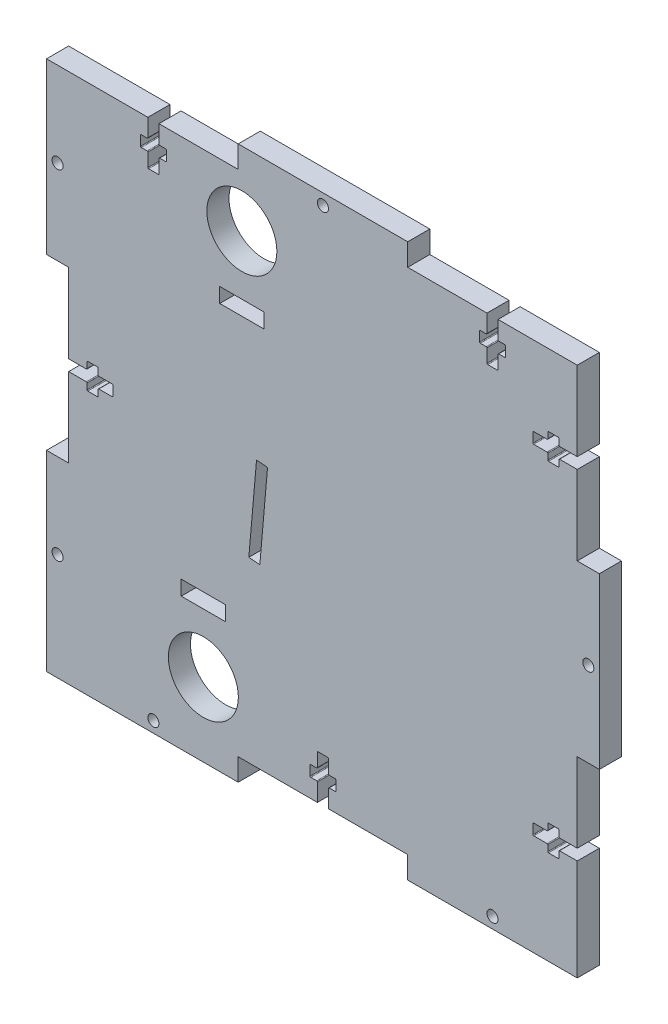
SolidWorks part; units mm, degrees
ref_plane "Front Plane" through (0, 0, 0) normal (0, 0, 1) x (1, 0, 0)
ref_plane "Top Plane" through (0, 0, 0) normal (0, 1, 0) x (1, 0, 0)
ref_plane "Right Plane" through (0, 0, 0) normal (1, 0, 0) x (0, 0, -1)
sketch "Sketch1" plane through (0, 0, 0) normal (0, 0, 1) x (1, 0, 0)
  line L0 (-69, 69) -> (-23, 69)
  line L5 (-75, -75) -> (75, -75) construction
  line L6 (-75, -75) -> (-75, 75) construction
  line L7 (-75, 75) -> (75, 75) construction
  line L8 (75, -75) -> (75, 75) construction
  line L9 (75, 23) -> (69, 23)
  line L10 (69, -23) -> (75, -23)
  line L11 (-69, -69) -> (69, -69) construction
  line L12 (-69, -69) -> (-69, 69) construction
  line L13 (-69, 69) -> (69, 69) construction
  line L14 (69, -69) -> (69, 69) construction
  line L15 (-69, -69) -> (69, 69) construction
  line L16 (69, -69) -> (69, -23)
  line L17 (-23, 69) -> (-23, 75)
  line L18 (-23, 75) -> (23, 75)
  line L19 (23, 75) -> (23, 69)
  line L20 (23, 69) -> (69, 69)
  line L21 (75, -23) -> (75, 23)
  line L22 (69, 23) -> (69, 69)
  line L23 (-75, 23) -> (-69, 23)
  line L24 (-69, 69) -> (-75, 69)
  line L25 (-75, 69) -> (-75, 23)
  line L26 (69, -69) -> (69, -75)
  line L27 (69, -75) -> (23, -75)
  line L28 (23, -75) -> (23, -69)
  line L29 (23, -69) -> (-23, -69)
  line L30 (-23, -69) -> (-23, -75)
  line L31 (-23, -75) -> (-69, -75)
  line L32 (-69, -75) -> (-69, -69) construction
  line L33 (-69, 23) -> (-69, -23)
  line L34 (-69, -23) -> (-75, -23)
  line L35 (-75, -23) -> (-75, -69)
  line L36 (-75, -69) -> (-69, -69) construction
  line L37 (-46, 69) -> (-46, -75) construction
  line L38 (-69, 69) -> (69, -69) construction
  line L39 (-75, -75) -> (-69, -75)
  line L40 (-75, -75) -> (-75, -69)
  point P0 (0, 0)
  point P6 (-7, -7)
  point P26 (0, -75)
  point P27 (-75, 0)
  dimension "D1" = 150
  dimension "D2" = 150
  dimension "D5" = 46
  dimension "D3" = 6
  dimension "D6" = 6
  dimension "D7" = 6
extrude "Box Side" add sketch "Sketch1" along normal blind 6
sketch "Sketch2" plane through (0, 0, 6) normal (0, 0, 1) x (1, 0, 0)
  line L0 (23, 72) -> (-23, 72) construction
  line L1 (23, 75) -> (23, 69) construction
  line L2 (-23, 69) -> (-23, 75) construction
  line L3 (-46, 69) -> (-46, -75) construction
  line L5 (0, 75) -> (0, 69) construction
  line L6 (-23, 75) -> (23, 75) construction
  line L7 (-69, 69) -> (69, 69) construction
  line L16 (-46, 69) -> (-46, -75) construction
  line L21 (0, -69) -> (0, 69) construction
  line L35 (-69, 69) -> (-23, 69) construction
  line L36 (-44.5, 69) -> (-44.5, 64.2)
  line L37 (-44.3, 64) -> (-42.7, 64)
  line L38 (-42.5, 63.8) -> (-42.5, 61.2)
  line L39 (-42.7, 61) -> (-44.3, 61)
  line L40 (-44.5, 60.8) -> (-44.5, 57.2)
  line L46 (-44.7, 57) -> (-47.3, 57)
  line L48 (-44.5, 69) -> (-47.5, 69)
  line L51 (-47.5, 60.8) -> (-47.5, 57.2)
  line L52 (-49.3, 61) -> (-47.7, 61)
  line L53 (-49.5, 63.8) -> (-49.5, 61.2)
  line L54 (-47.7, 64) -> (-49.3, 64)
  line L55 (-47.5, 69) -> (-47.5, 64.2)
  line L56 (47.5, 69) -> (47.5, 64.2)
  line L57 (47.7, 64) -> (49.3, 64)
  line L58 (49.5, 63.8) -> (49.5, 61.2)
  line L59 (49.3, 61) -> (47.7, 61)
  line L60 (47.5, 60.8) -> (47.5, 57.2)
  line L61 (44.5, 69) -> (47.5, 69)
  line L62 (44.7, 57) -> (47.3, 57)
  line L63 (44.5, 60.8) -> (44.5, 57.2)
  line L64 (42.7, 61) -> (44.3, 61)
  line L65 (42.5, 63.8) -> (42.5, 61.2)
  line L66 (44.3, 64) -> (42.7, 64)
  line L67 (44.5, 69) -> (44.5, 64.2)
  line L68 (-69, -69) -> (69, 69) construction
  line L69 (-69, -69) -> (69, 69) construction
  line L70 (75, 0) -> (69, 0) construction
  line L71 (72, 23) -> (72, -23) construction
  line L72 (69, 44.5) -> (64.2, 44.5)
  line L73 (64, 44.3) -> (64, 42.7)
  line L74 (63.8, 42.5) -> (61.2, 42.5)
  line L75 (61, 42.7) -> (61, 44.3)
  line L76 (60.8, 44.5) -> (57.2, 44.5)
  line L77 (57, 44.7) -> (57, 47.3)
  line L78 (69, 44.5) -> (69, 47.5)
  line L79 (60.8, 47.5) -> (57.2, 47.5)
  line L80 (61, 49.3) -> (61, 47.7)
  line L81 (63.8, 49.5) -> (61.2, 49.5)
  line L82 (64, 47.7) -> (64, 49.3)
  line L83 (69, 47.5) -> (64.2, 47.5)
  line L84 (69, -47.5) -> (64.2, -47.5)
  line L85 (64, -47.7) -> (64, -49.3)
  line L86 (63.8, -49.5) -> (61.2, -49.5)
  line L87 (61, -49.3) -> (61, -47.7)
  line L88 (60.8, -47.5) -> (57.2, -47.5)
  line L89 (69, -44.5) -> (69, -47.5)
  line L90 (57, -44.7) -> (57, -47.3)
  line L91 (60.8, -44.5) -> (57.2, -44.5)
  line L92 (61, -42.7) -> (61, -44.3)
  line L93 (63.8, -42.5) -> (61.2, -42.5)
  line L94 (64, -44.3) -> (64, -42.7)
  line L95 (69, -44.5) -> (64.2, -44.5)
  line L120 (-69, 69) -> (69, -69) construction
  line L121 (-69, 69) -> (69, -69) construction
  line L122 (-1.5, -69) -> (1.5, -69)
  line L123 (-23, -69) -> (23, -69) construction
  line L124 (1.5, -69) -> (1.5, -64.2)
  line L125 (1.7, -64) -> (3.3, -64)
  line L126 (3.5, -63.8) -> (3.5, -61.2)
  line L127 (3.3, -61) -> (1.7, -61)
  line L128 (1.5, -60.8) -> (1.5, -57.2)
  line L129 (1.3, -57) -> (-1.3, -57)
  line L130 (-1.5, -60.8) -> (-1.5, -57.2)
  line L131 (-3.3, -61) -> (-1.7, -61)
  line L132 (-3.5, -63.8) -> (-3.5, -61.2)
  line L133 (-1.7, -64) -> (-3.3, -64)
  line L134 (-1.5, -69) -> (-1.5, -64.2)
  line L135 (-69, -1.5) -> (-64.2, -1.5)
  line L136 (-64, -1.7) -> (-64, -3.3)
  line L137 (-63.8, -3.5) -> (-61.2, -3.5)
  line L138 (-61, -3.3) -> (-61, -1.7)
  line L139 (-60.8, -1.5) -> (-57.2, -1.5)
  line L140 (-57, 1.3) -> (-57, -1.3)
  line L141 (-60.8, 1.5) -> (-57.2, 1.5)
  line L142 (-61, 3.3) -> (-61, 1.7)
  line L143 (-63.8, 3.5) -> (-61.2, 3.5)
  line L144 (-64, 1.7) -> (-64, 3.3)
  line L145 (-69, 1.5) -> (-64.2, 1.5)
  line L146 (-69, -1.5) -> (-69, 1.5)
  line L147 (-69, -72) -> (-23, -72) construction
  line L148 (-23, 69) -> (-75, 69) construction
  line L149 (-23, -75) -> (-23, -69) construction
  line L150 (-69, -69) -> (-69, -75) construction
  line L151 (-75, -75) -> (-23, -75) construction
  circle A0 centre (0, 72) radius 1.5
  arc A1 (-44.5, 57.2) -> (-44.7, 57) centre (-44.7, 57.2) cw
  arc A2 (-44.3, 61) -> (-44.5, 60.8) centre (-44.3, 60.8) ccw
  arc A3 (-42.5, 61.2) -> (-42.7, 61) centre (-42.7, 61.2) cw
  arc A4 (-42.7, 64) -> (-42.5, 63.8) centre (-42.7, 63.8) cw
  arc A5 (-44.5, 64.2) -> (-44.3, 64) centre (-44.3, 64.2) ccw
  arc A6 (-47.5, 64.2) -> (-47.7, 64) centre (-47.7, 64.2) cw
  arc A7 (-49.3, 64) -> (-49.5, 63.8) centre (-49.3, 63.8) ccw
  arc A8 (-49.5, 61.2) -> (-49.3, 61) centre (-49.3, 61.2) ccw
  arc A9 (-47.7, 61) -> (-47.5, 60.8) centre (-47.7, 60.8) cw
  arc A10 (-47.5, 57.2) -> (-47.3, 57) centre (-47.3, 57.2) ccw
  arc A11 (47.5, 57.2) -> (47.3, 57) centre (47.3, 57.2) cw
  arc A12 (47.7, 61) -> (47.5, 60.8) centre (47.7, 60.8) ccw
  arc A13 (49.5, 61.2) -> (49.3, 61) centre (49.3, 61.2) cw
  arc A14 (49.3, 64) -> (49.5, 63.8) centre (49.3, 63.8) cw
  arc A15 (47.5, 64.2) -> (47.7, 64) centre (47.7, 64.2) ccw
  arc A16 (44.5, 64.2) -> (44.3, 64) centre (44.3, 64.2) cw
  arc A17 (42.7, 64) -> (42.5, 63.8) centre (42.7, 63.8) ccw
  arc A18 (42.5, 61.2) -> (42.7, 61) centre (42.7, 61.2) ccw
  arc A19 (44.3, 61) -> (44.5, 60.8) centre (44.3, 60.8) cw
  arc A20 (44.5, 57.2) -> (44.7, 57) centre (44.7, 57.2) ccw
  arc A21 (57.2, 44.5) -> (57, 44.7) centre (57.2, 44.7) cw
  arc A22 (61, 44.3) -> (60.8, 44.5) centre (60.8, 44.3) ccw
  arc A23 (61.2, 42.5) -> (61, 42.7) centre (61.2, 42.7) cw
  arc A24 (64, 42.7) -> (63.8, 42.5) centre (63.8, 42.7) cw
  arc A25 (64.2, 44.5) -> (64, 44.3) centre (64.2, 44.3) ccw
  arc A26 (64.2, 47.5) -> (64, 47.7) centre (64.2, 47.7) cw
  arc A27 (64, 49.3) -> (63.8, 49.5) centre (63.8, 49.3) ccw
  arc A28 (61.2, 49.5) -> (61, 49.3) centre (61.2, 49.3) ccw
  arc A29 (61, 47.7) -> (60.8, 47.5) centre (60.8, 47.7) cw
  arc A30 (57.2, 47.5) -> (57, 47.3) centre (57.2, 47.3) ccw
  arc A31 (57.2, -47.5) -> (57, -47.3) centre (57.2, -47.3) cw
  arc A32 (61, -47.7) -> (60.8, -47.5) centre (60.8, -47.7) ccw
  arc A33 (61.2, -49.5) -> (61, -49.3) centre (61.2, -49.3) cw
  arc A34 (64, -49.3) -> (63.8, -49.5) centre (63.8, -49.3) cw
  arc A35 (64.2, -47.5) -> (64, -47.7) centre (64.2, -47.7) ccw
  arc A36 (64.2, -44.5) -> (64, -44.3) centre (64.2, -44.3) cw
  arc A37 (64, -42.7) -> (63.8, -42.5) centre (63.8, -42.7) ccw
  arc A38 (61.2, -42.5) -> (61, -42.7) centre (61.2, -42.7) ccw
  arc A39 (61, -44.3) -> (60.8, -44.5) centre (60.8, -44.3) cw
  arc A40 (57.2, -44.5) -> (57, -44.7) centre (57.2, -44.7) ccw
  circle A41 centre (72, 0) radius 1.5
  arc A62 (1.5, -57.2) -> (1.3, -57) centre (1.3, -57.2) ccw
  arc A63 (1.7, -61) -> (1.5, -60.8) centre (1.7, -60.8) cw
  arc A64 (3.5, -61.2) -> (3.3, -61) centre (3.3, -61.2) ccw
  arc A65 (3.3, -64) -> (3.5, -63.8) centre (3.3, -63.8) ccw
  arc A66 (1.5, -64.2) -> (1.7, -64) centre (1.7, -64.2) cw
  arc A67 (-1.5, -64.2) -> (-1.7, -64) centre (-1.7, -64.2) ccw
  arc A68 (-3.3, -64) -> (-3.5, -63.8) centre (-3.3, -63.8) cw
  arc A69 (-3.5, -61.2) -> (-3.3, -61) centre (-3.3, -61.2) cw
  arc A70 (-1.7, -61) -> (-1.5, -60.8) centre (-1.7, -60.8) ccw
  arc A71 (-1.5, -57.2) -> (-1.3, -57) centre (-1.3, -57.2) cw
  arc A72 (-57.2, -1.5) -> (-57, -1.3) centre (-57.2, -1.3) ccw
  arc A73 (-61, -1.7) -> (-60.8, -1.5) centre (-60.8, -1.7) cw
  arc A74 (-61.2, -3.5) -> (-61, -3.3) centre (-61.2, -3.3) ccw
  arc A75 (-64, -3.3) -> (-63.8, -3.5) centre (-63.8, -3.3) ccw
  arc A76 (-64.2, -1.5) -> (-64, -1.7) centre (-64.2, -1.7) cw
  arc A77 (-64.2, 1.5) -> (-64, 1.7) centre (-64.2, 1.7) ccw
  arc A78 (-64, 3.3) -> (-63.8, 3.5) centre (-63.8, 3.3) cw
  arc A79 (-61.2, 3.5) -> (-61, 3.3) centre (-61.2, 3.3) cw
  arc A80 (-61, 1.7) -> (-60.8, 1.5) centre (-60.8, 1.7) ccw
  arc A81 (-57.2, 1.5) -> (-57, 1.3) centre (-57.2, 1.3) cw
  circle A82 centre (-46, -72) radius 1.5
  circle A83 centre (46, -72) radius 1.5
  circle A84 centre (-72, 46) radius 1.5
  circle A85 centre (-72, -46) radius 1.5
  point P6 (0, 72)
  point P38 (0, 0)
  point P56 (-46, 57)
  point P88 (46, 57)
  point P161 (57, 46)
  point P162 (57, -46)
  point P198 (0, -57)
  point P231 (-57, 0)
  point P234 (-42.5, 62.5)
  dimension "D1" = 3
  dimension "D2" = 0.2
  dimension "D8" = 0.2
  dimension "D14" = 3
  dimension "D4" = 3
  dimension "D7" = 1.5
  dimension "D10" = 3
  dimension "D12" = 1.5
  dimension "D9" = 12
  dimension "D11" = 5
  dimension "D13" = 7
  dimension "D3" = 12
  dimension "D5" = 7
  dimension "D6" = 5
extrude "Screw Cut-outs" cut sketch "Sketch2" against normal through all
sketch "Sketch3" plane through (0, 0, 6) normal (0, 0, 1) x (1, 0, 0)
  line L0 (-23, 69) -> (-44.5, 69) construction
  line L1 (-69, 23) -> (-69, 1.5) construction
  circle A0 centre (-22, 55) radius 9.5
  circle A1 centre (-32.45, -55) radius 9.5
  circle A2 centre (-32.45, -55) radius 6.5 construction
  dimension "D1" = 19
  dimension "D4" = 19
  dimension "D7" = 13
  dimension "D2" = 14
  dimension "D3" = 47
  dimension "D5" = 10.45
  dimension "D6" = 110
extrude "Cut-Extrude1" cut sketch "Sketch3" against normal through all
sketch "Sketch4" plane through (0, 0, 6) normal (0, 0, 1) x (1, 0, 0)
  line L0 (-24.9996, 51) -> (49975.0004, 51) construction
  line L1 (-23, 69) -> (-44.5, 69) construction
  line L2 (-13.84, 51) -> (-13.84, 69) construction
  line L3 (69, 47.5) -> (69, 69) construction
  line L4 (-13.84, 51) -> (-25.7981, -85.6815) construction
  line L5 (-13.84, 51) -> (49795.8949, -4306.7871) construction
  line L6 (-10.8514, 50.7385) -> (-4368.6386, -49758.9964) construction
  line L7 (-20.1126, -20.6961) -> (-17.124, -20.9576)
  line L8 (-17.124, -20.9576) -> (-15.0323, 2.9511)
  line L9 (-15.0323, 2.9511) -> (-18.0209, 3.2125)
  line L10 (-18.0209, 3.2125) -> (-20.1126, -20.6961)
  dimension "D1" = 18
  dimension "D2" = 82.84
  dimension "D3" = 5
  dimension "D4" = 3
  dimension "D5" = 24
  dimension "D6" = 47.97
extrude "Cut-Extrude2" cut sketch "Sketch4" against normal through all
sketch "Sketch5" plane through (0, 0, 6) normal (0, 0, 1) x (1, 0, 0)
  line L1 (-38.45, -39) -> (-26.45, -39)
  line L2 (-38.45, -39) -> (-38.45, -35)
  line L3 (-38.45, -35) -> (-26.45, -35)
  line L4 (-26.45, -39) -> (-26.45, -35)
  line L5 (-28, 35) -> (-16, 35)
  line L6 (-28, 35) -> (-28, 39)
  line L7 (-28, 39) -> (-16, 39)
  line L8 (-16, 35) -> (-16, 39)
  point P8 (-32.45, -55)
  point P9 (-22, 55)
  point P11 (-22, 39)
  point P13 (-32.45, -39)
  dimension "D1" = 16
  dimension "D2" = 16
  dimension "D3" = 4
  dimension "D4" = 12
extrude "Cut-Extrude3" cut sketch "Sketch5" against normal through all
equation "\"filletRadius\"=0.2"
equation "\"D8@Sketch2\"=\"filletRadius\""
equation "\"D2@Sketch2\"=\"filletRadius\""
equation "\"fingerWidth\"= 46"
equation "\"D5@Sketch1\"=\"fingerWidth\""
equation "\"wallThickness\"= 6"
equation "\"D3@Sketch1\" = \"wallThickness\""
equation "\"D6@Sketch1\" = \"wallThickness\""
equation "\"D7@Sketch1\" = \"wallThickness\""
equation "\"D1@Box Side\" = \"wallThickness\""
equation "\"M3\"= 3"
equation "\"D14@Sketch2\"=\"M3\""
equation "\"D1@Sketch2\"=\"M3\""
equation "\"D12@Sketch2\"=\"M3\"/2"
equation "\"nutThickness\"=3"
equation "\"D10@Sketch2\" = \"nutThickness\""
equation "\"boltLength\"= 12"
equation "\"D9@Sketch2\" = \"boltLength\""
equation "\"distanceToNut\"= 5"
equation "\"D11@Sketch2\" = \"distanceToNut\""
equation "\"D13@Sketch2\" = \"nutWidth\""
equation "\"D7@Sketch2\"=\"M3\"/2"
equation "\"D4@Sketch2\" = \"nutThickness\""
equation "\"D3@Sketch2\" = \"boltLength\""
equation "\"D5@Sketch2\" = \"nutWidth\""
equation "\"D6@Sketch2\" = \"distanceToNut\""
equation "\"sideLength\"=150"
equation "\"D1@Sketch1\"=\"sideLength\""
equation "\"D2@Sketch1\"=\"sideLength\""
equation "\"nutWidth\"=7"
